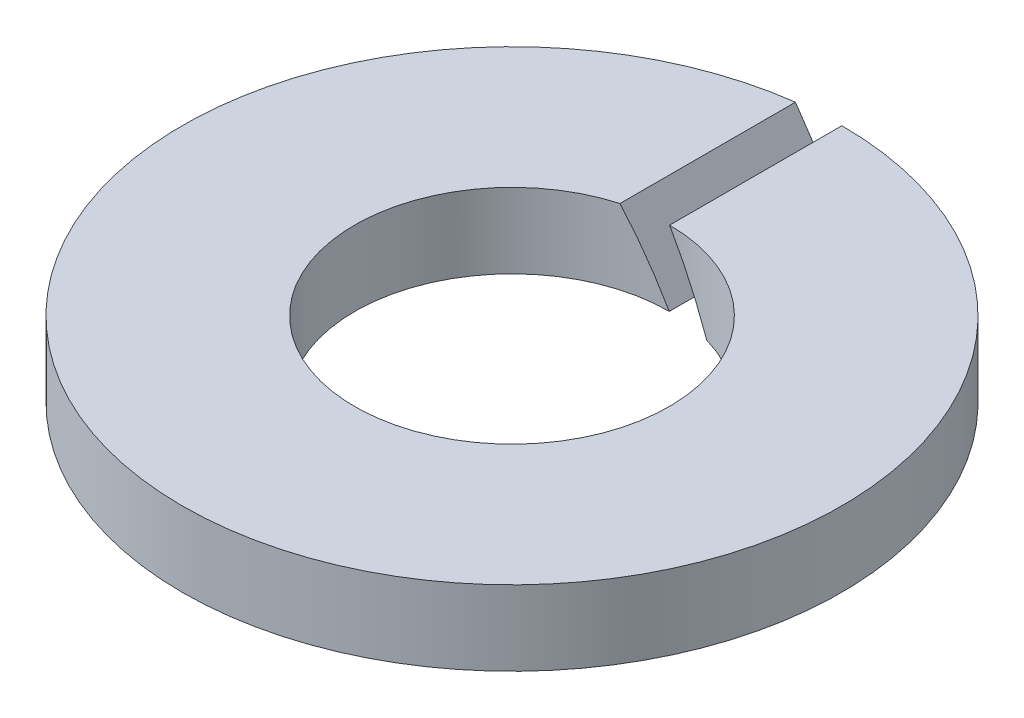
SolidWorks part; units mm, degrees
ref_plane "Front Plane" through (0, 0, 0) normal (0, 0, 1) x (1, 0, 0)
ref_plane "Top Plane" through (0, 0, 0) normal (0, 1, 0) x (1, 0, 0)
ref_plane "Right Plane" through (0, 0, 0) normal (1, 0, 0) x (0, 0, -1)
sketch "BoseSke" plane through (0, 0, 0) normal (0, 1, 0) x (1, 0, 0)
  circle A0 centre (0, 0) radius 1.05
  circle A1 centre (0, 0) radius 2.2
extrude "BaseBody" add sketch "BoseSke" along normal blind 0.5
sketch "SlitSke" plane through (0, 0, 0) normal (0, 0, 1) x (1, 0, 0)
  line L0 (0, 0) -> (-0.2887, 0.5)
  line L1 (1.05, 0.5) -> (-1.05, 0.5) construction
  line L2 (-0.2887, 0.5) -> (0.0023, 0.5)
  line L3 (2.2, 0.5) -> (-2.2, 0.5) construction
  line L4 (0.0023, 0.5) -> (0.291, 0)
  line L5 (-2.2, 0) -> (2.2, 0) construction
  line L6 (0.291, 0) -> (0, 0)
  dimension "D1" = 0.252
extrude "Slit" cut sketch "SlitSke" against normal through all
equation "\"D1@SlitSke\" = \"Inner_dia@BoseSke\" * 0.12"
